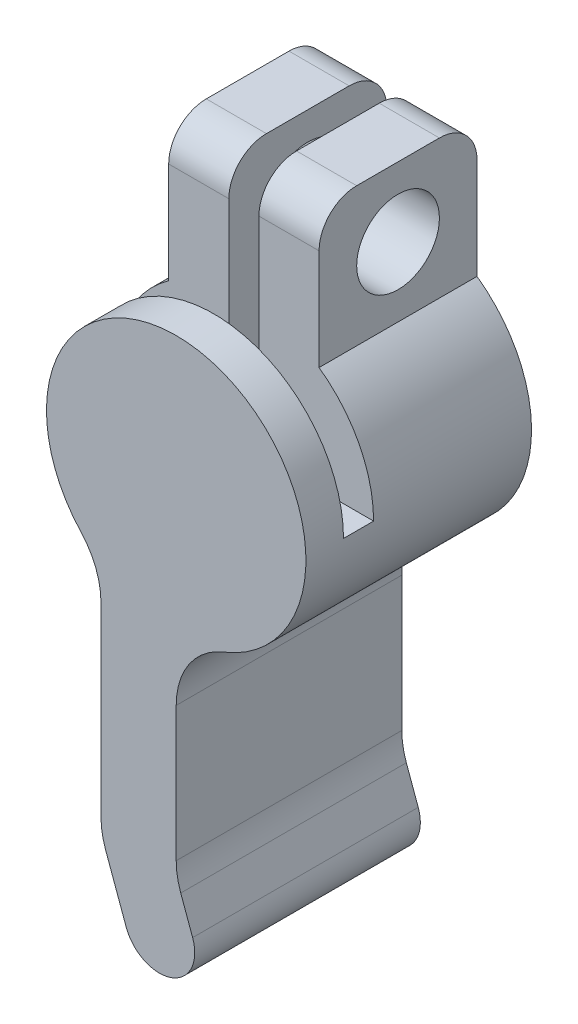
SolidWorks part; units mm, degrees
material "ABS"
ref_plane "Front Plane" through (0, 0, 0) normal (0, 0, 1) x (1, 0, 0)
ref_plane "Top Plane" through (0, 0, 0) normal (0, 1, 0) x (1, 0, 0)
ref_plane "Right Plane" through (0, 0, 0) normal (1, 0, 0) x (0, 0, -1)
sketch "Sketch1" plane through (0, 0, 0) normal (0, 0, 1) x (1, 0, 0)
  line L0 (0, -9) -> (0, -3.45)
  line L1 (-2, -9) -> (-2, -2.8111)
  line L2 (0, -9) -> (0.4368, -10.2)
  line L4 (-1.3293, -10.8428) -> (-2, -9)
  line L5 (-2, -9) -> (0, -9) construction
  line L6 (-1.3293, -10.8428) -> (0.4368, -10.2) construction
  line L9 (-0.4, 1.3937) -> (-0.4, 6.5)
  line L10 (-0.4, 6.5) -> (-2, 6.5)
  line L11 (-2, 6.5) -> (-2, 2.8111)
  line L12 (0.4, 1.3937) -> (0.4, 6.5)
  line L13 (0.4, 6.5) -> (2, 6.5)
  line L14 (2, 6.5) -> (2, 2.8111)
  arc A0 (-0.4, 1.3937) -> (0.4, 1.3937) centre (0, 0) ccw
  arc A2 (0, -3.45) -> (2, 2.8111) centre (0, 0) ccw
  circle A4 centre (0, 0) radius 3.45 construction
  arc A5 (-1.3293, -10.8428) -> (0.4368, -10.2) centre (-0.4463, -10.5214) ccw
  arc A6 (-2, 2.8111) -> (-2, -2.8111) centre (0, 0) ccw
  circle A7 centre (0, 0) radius 1.45 construction
  point P3 (-1, -9)
  dimension "D1" = 2.9
  dimension "D4" = 1.2
  dimension "D6" = 160
  dimension "D7" = 0.8
  dimension "D2" = 2
  dimension "D3" = 9
  dimension "D8" = 1.6
  dimension "D9" = 6.5
  dimension "D5" = 2
extrude "Boss-Extrude1" add sketch "Sketch1" along normal blind 4.2 contours A2 A0 | A2 region at (0.0376, -9.6658, 0)
sketch "Sketch2" plane through (-2, 0, 0) normal (-1, 0, 0) x (0, 0, 1)
  line L0 (4.2, 6.5) -> (0, 6.5) construction
  line L7 (0, 6.5) -> (0, 2.8111) construction
  circle A0 centre (2.1, 4.6556) radius 1.1
  point P2 (2.1, 6.5)
  point P3 (0, 4.6556)
  dimension "D1" = 2.2
extrude "Cut-Extrude1" cut sketch "Sketch2" against normal through all
fillet "Fillet1" radius 1 4 edges at (1.2, 6.5, 4.2) (1.2, 6.5, 0) (-1.2, 6.5, 4.2) (-1.2, 6.5, 0)
sketch "Sketch3" plane through (0, 0, 4.2) normal (0, 0, 1) x (1, 0, 0)
  line L0 (-3.45, 0) -> (-1.45, 0)
  line L1 (1.45, 0) -> (3.45, 0)
  line L10 (2, 2.8111) -> (2, 5.5)
  line L11 (2, 5.5) -> (0.4, 5.5)
  line L12 (0.4, 5.5) -> (0.4, 1.3937)
  line L13 (-0.4, 1.3937) -> (-0.4, 5.5)
  line L14 (-0.4, 5.5) -> (-2, 5.5)
  line L15 (-2, 5.5) -> (-2, 2.8111)
  line L16 (-2, -2.8111) -> (-2, -9)
  line L17 (-2, -9) -> (-1.3293, -10.8428)
  line L18 (0.4368, -10.2) -> (0, -9)
  line L19 (0, -9) -> (0, -3.45)
  line L22 (0.4, 5.5) -> (0.4, 1.3937)
  line L26 (-2, -2.8111) -> (-2, -9)
  line L27 (-2, -9) -> (-1.3293, -10.8428)
  line L28 (0.4368, -10.2) -> (0, -9)
  line L29 (0, -9) -> (0, -3.45)
  arc A4 (-0.4, 1.3937) -> (0.4, 1.3937) centre (0, 0) ccw
  arc A5 (-2, 2.8111) -> (-2, -2.8111) centre (0, 0) ccw
  arc A6 (-1.3293, -10.8428) -> (0.4368, -10.2) centre (-0.4463, -10.5214) ccw
  arc A7 (0, -3.45) -> (2, 2.8111) centre (0, 0) ccw
  arc A8 (-1.45, 0) -> (1.45, 0) centre (0, 0) ccw
  arc A9 (-3.45, 0) -> (-2, -2.8111) centre (0, 0) ccw
  arc A10 (-1.3293, -10.8428) -> (0.4368, -10.2) centre (-0.4463, -10.5214) ccw
  arc A11 (0, -3.45) -> (3.45, 0) centre (0, 0) ccw
  arc M18 (0.4, 1.3937) -> (-0.4, 1.3937) centre (0, 0) cw
  arc M22 (-2, 2.8111) -> (-2, -2.8111) centre (0, 0) ccw
  line M23 (-2, -2.8111) -> (-2, -9)
  line M24 (-2, -9) -> (-1.3293, -10.8428)
  arc M25 (-1.3293, -10.8428) -> (0.4368, -10.2) centre (-0.4463, -10.5214) ccw
  line M26 (0.4368, -10.2) -> (0, -9)
  line M27 (0, -9) -> (0, -3.45)
  arc M28 (0, -3.45) -> (2, 2.8111) centre (0, 0) ccw
  dimension "D1" = 0
extrude "Boss-Extrude2" add sketch "Sketch3" along normal blind 0.8 contours L1 L0 M18 M22 M23 M24 M25 M26 M27 M28 region at (-0.4643, -4.4881, 4.2)
sketch "Sketch4" plane through (0, 0, 5) normal (0, 0, 1) x (1, 0, 0)
  line L4 (1.45, 0) -> (3.45, 0)
  line L5 (2, 2.8111) -> (2, 5.5)
  line L6 (3.45, 0) -> (1.45, 0)
  line L7 (-1.45, 0) -> (-3.45, 0)
  line L8 (-2, -2.8111) -> (-2, -9)
  line L9 (-2, -9) -> (-1.3293, -10.8428)
  line L10 (0.4368, -10.2) -> (0, -9)
  line L11 (0, -9) -> (0, -3.45)
  line L14 (-2, -2.8111) -> (-2, -9)
  line L15 (-2, -9) -> (-1.3293, -10.8428)
  line L16 (0.4368, -10.2) -> (0, -9)
  line L17 (0, -9) -> (0, -3.45)
  line L18 (2, 5.5) -> (0.4, 5.5)
  line L19 (0.4, 5.5) -> (0.4, 1.3937)
  line L24 (-3.45, 0) -> (-1.45, 0)
  line L25 (-0.4, 1.3937) -> (-0.4, 5.5)
  line L26 (-0.4, 5.5) -> (-2, 5.5)
  line L27 (-2, 5.5) -> (-2, 2.8111)
  arc A2 (3.45, 0) -> (2, 2.8111) centre (0, 0) ccw
  arc A3 (1.45, 0) -> (0.4, 1.3937) centre (0, 0) ccw
  arc A4 (-1.45, 0) -> (1.45, 0) centre (0, 0) ccw
  arc A5 (-3.45, 0) -> (-2, -2.8111) centre (0, 0) ccw
  arc A6 (-1.3293, -10.8428) -> (0.4368, -10.2) centre (-0.4463, -10.5214) ccw
  arc A7 (0, -3.45) -> (3.45, 0) centre (0, 0) ccw
  arc A8 (-1.45, 0) -> (1.45, 0) centre (0, 0) ccw
  arc A9 (-3.45, 0) -> (-2, -2.8111) centre (0, 0) ccw
  arc A10 (-1.3293, -10.8428) -> (0.4368, -10.2) centre (-0.4463, -10.5214) ccw
  arc A11 (0, -3.45) -> (3.45, 0) centre (0, 0) ccw
  arc A12 (3.45, 0) -> (2, 2.8111) centre (0, 0) ccw
  arc A13 (1.45, 0) -> (0.4, 1.3937) centre (0, 0) ccw
  arc A14 (-0.4, 1.3937) -> (-1.45, 0) centre (0, 0) ccw
  arc A15 (-2, 2.8111) -> (-3.45, 0) centre (0, 0) ccw
  arc A16 (0.4, 1.3937) -> (-1.45, 0) centre (0, 0) ccw
  arc A17 (2, 2.8111) -> (-3.45, 0) centre (0, 0) ccw
  line M23 (3.45, 0) -> (1.45, 0)
  arc M24 (1.45, 0) -> (-1.45, 0) centre (0, 0) cw
  line M25 (-1.45, 0) -> (-3.45, 0)
  arc M26 (-3.45, 0) -> (-2, -2.8111) centre (0, 0) ccw
  line M27 (-2, -2.8111) -> (-2, -9)
  line M28 (-2, -9) -> (-1.3293, -10.8428)
  arc M29 (-1.3293, -10.8428) -> (0.4368, -10.2) centre (-0.4463, -10.5214) ccw
  line M30 (0.4368, -10.2) -> (0, -9)
  line M31 (0, -9) -> (0, -3.45)
  arc M32 (0, -3.45) -> (3.45, 0) centre (0, 0) ccw
  dimension "D1" = 0
  dimension "D2" = 0
  dimension "D3" = 0
extrude "Boss-Extrude3" add sketch "Sketch4" along normal blind 1 contours A13 A16 M24 | A12 A17 A16 A13 M25 M23 | M32 M23 M24 M25 M26 M27 M28 M29 M30 M31 region at (1.8151, 1.5541, 5) region at (0, 0, 5) region at (-0.4643, -4.4881, 5) region at (0, 2.4368, 5) region at (-1.8151, 1.5541, 5)
fillet "Fillet2" radius 2 4 edges at (-2, -9, 3) (0, -9, 3) (0, -3.45, 3) (-2, -2.8111, 3)
